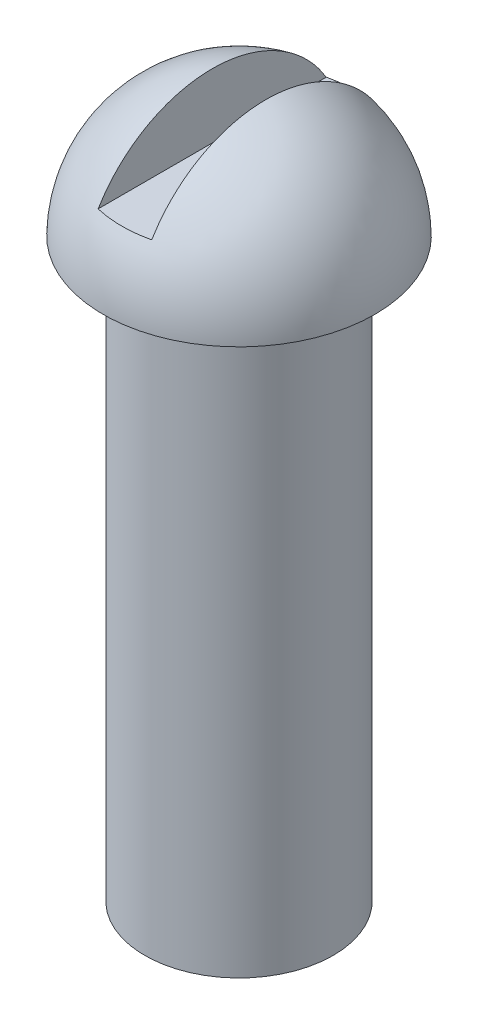
SolidWorks part; units mm, degrees
material "PW90:Mi:0:238:Ar:0:-1:C1:1:2:3:Re:27:"
ref_plane "Front" through (0, 0, 0) normal (0, 0, 1) x (1, 0, 0)
ref_plane "Top" through (0, 0, 0) normal (0, 1, 0) x (1, 0, 0)
ref_plane "Right" through (0, 0, 0) normal (1, 0, 0) x (0, 0, -1)
sketch "Sketch1" plane through (0, 0, 0) normal (0, 0, 1) x (1, 0, 0)
  line L0 (0, 10.1105) -> (0, -21.844) construction
  line L1 (5.1562, 0) -> (3.5719, 0)
  line L2 (3.5719, 0) -> (3.5719, -21.844)
  line L3 (3.5719, -21.844) -> (0, -21.844)
  line L4 (0, -21.844) -> (0, 5.08)
  line L5 (0, 5.08) -> (-4.8734, 5.08) construction
  line L6 (50, 0) -> (-50, 0) construction
  arc A0 (0, 5.08) -> (5.1562, 0) centre (0, -0.0768) cw
  dimension "D1" = 10.3124
  dimension "D2" = 7.1437
  dimension "D3" = 26.924
  dimension "D4" = 5.08
revolve "Base-Revolve" add sketch "Sketch1" angle 360 about L0
sketch "Sketch2" plane through (0, 0, 0) normal (0, 0, 1) x (1, 0, 0)
  line L1 (-1.016, 4.9789) -> (-1.016, 2.54)
  line L2 (1.016, 2.54) -> (-1.016, 2.54)
  line L3 (1.016, 2.54) -> (1.016, 4.9789)
  line L5 (0, 2.9275) -> (0, -3.9159) construction
  line L6 (0, -21.844) -> (0, 0) construction
  arc A0 (5.1562, 0) -> (-5.1562, 0) centre (0, -0.0768) ccw construction
  arc A4 (1.016, 4.9789) -> (-1.016, 4.9789) centre (0, -0.0768) ccw
  dimension "D1" = 2.032
  dimension "D2" = 2.54
extrude "Cut-Extrude1" cut sketch "Sketch2" against normal through all and the other way through all
